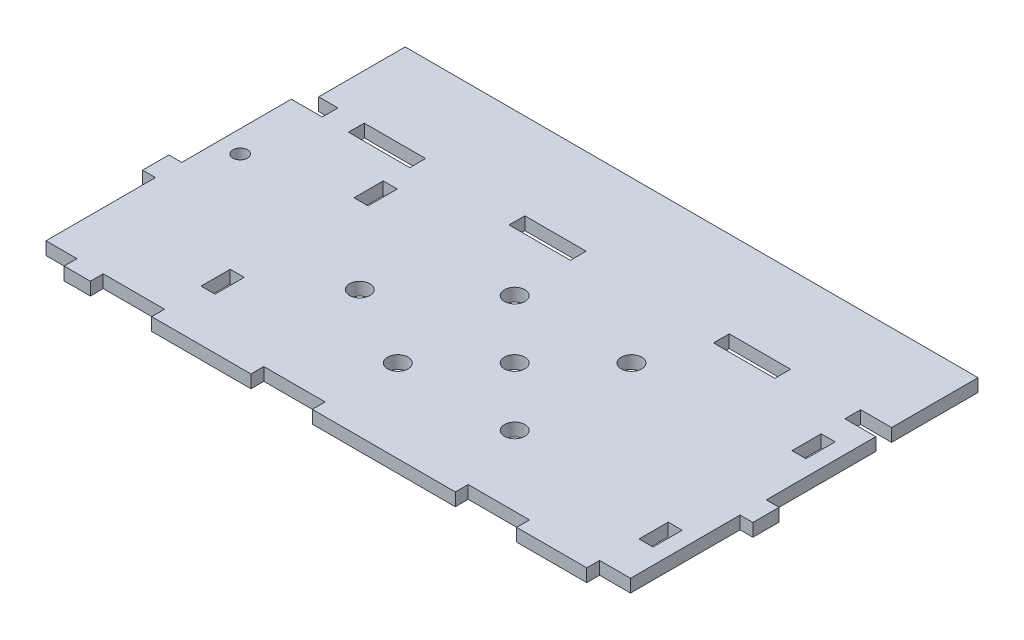
SolidWorks part; units mm, degrees
ref_plane "Front Plane" through (0, 0, 0) normal (0, 0, 1) x (1, 0, 0)
ref_plane "Top Plane" through (0, 0, 0) normal (0, 1, 0) x (1, 0, 0)
ref_plane "Right Plane" through (0, 0, 0) normal (1, 0, 0) x (0, 0, -1)
sketch "Sketch1" plane through (0, 0, 0) normal (0, 1, 0) x (1, 0, 0)
  line L0 (-110.6901, 12.3801) -> (-116.2781, 12.3801)
  line L2 (-110.6901, -46.6749) -> (-110.6901, 0.9501)
  line L4 (143.5639, -46.6749) -> (143.5639, 0.9501)
  line L5 (-110.6901, -46.6749) -> (143.5639, 60.0051) construction
  line L6 (-110.6901, 60.0051) -> (143.5639, -46.6749) construction
  line L7 (-116.2781, 12.3801) -> (-116.2781, 0.9501)
  line L8 (-116.2781, 0.9501) -> (-110.6901, 0.9501)
  line L9 (-110.6901, 12.3801) -> (-110.6901, 60.0051)
  line L10 (10.7219, 63.4341) -> (72.9519, 63.4341) construction
  line L11 (149.1519, 0.9501) -> (143.5639, 0.9501)
  line L12 (149.1519, 12.3801) -> (149.1519, 0.9501)
  line L13 (143.5639, 12.3801) -> (149.1519, 12.3801)
  line L14 (143.5639, 12.3801) -> (143.5639, 60.0051)
  line L23 (-108.712, 0) -> (106.818, 0) construction
  line L32 (-110.6901, 60.0051) -> (-97.2281, 60.0051)
  line L33 (-110.6901, -46.6749) -> (-97.2281, -46.6749)
  line L34 (-85.7981, 60.0051) -> (-59.1281, 60.0051)
  line L36 (-97.2281, 60.0051) -> (-97.2281, 66.8631)
  line L38 (-85.7981, 60.0051) -> (-85.7981, 66.8631)
  line L40 (-59.1281, 60.0051) -> (-59.1281, 66.8631)
  line L42 (-15.9481, 60.0051) -> (-15.9481, 66.8631)
  line L44 (10.7219, 60.0051) -> (10.7219, 66.8631)
  line L46 (72.9519, 60.0051) -> (72.9519, 66.8631)
  line L48 (99.6219, 60.0051) -> (99.6219, 66.8631)
  line L50 (130.1019, 60.0051) -> (130.1019, 66.8631)
  line L51 (-15.9481, 60.0051) -> (10.7219, 60.0051)
  line L52 (72.9519, 60.0051) -> (99.6219, 60.0051)
  line L53 (130.1019, 60.0051) -> (143.5639, 60.0051)
  line L54 (130.1019, -46.6749) -> (130.1019, -52.2629)
  line L55 (99.6219, -52.2629) -> (130.1019, -52.2629)
  line L56 (99.6219, -46.6749) -> (99.6219, -52.2629)
  line L57 (72.9519, -46.6749) -> (72.9519, -52.2629)
  line L58 (10.7219, -52.2629) -> (72.9519, -52.2629)
  line L59 (10.7219, -46.6749) -> (10.7219, -52.2629)
  line L60 (-15.9481, -46.6749) -> (-15.9481, -52.2629)
  line L61 (-59.1281, -52.2629) -> (-15.9481, -52.2629)
  line L62 (-59.1281, -46.6749) -> (-59.1281, -52.2629)
  line L63 (-85.7981, -46.6749) -> (-85.7981, -52.2629)
  line L64 (-97.2281, -52.2629) -> (-85.7981, -52.2629)
  line L65 (-97.2281, -46.6749) -> (-97.2281, -52.2629)
  line L66 (-85.7981, -46.6749) -> (-59.1281, -46.6749)
  line L67 (-15.9481, -46.6749) -> (10.7219, -46.6749)
  line L68 (72.9519, -46.6749) -> (99.6219, -46.6749)
  line L69 (130.1019, -46.6749) -> (143.5639, -46.6749)
  line L70 (130.1019, 66.8631) -> (143.5639, 66.8631)
  line L71 (143.5639, 66.8631) -> (143.5639, 104.4551)
  line L72 (-97.2281, 66.8631) -> (-105.6101, 66.8631)
  line L73 (-105.6101, 66.8631) -> (-105.6101, 104.4551)
  line L74 (-105.6101, 104.4551) -> (143.5639, 104.4551)
  line L75 (99.6219, 66.8631) -> (72.9519, 66.8631)
  line L76 (10.7219, 66.8631) -> (-15.9481, 66.8631)
  line L77 (-59.1281, 66.8631) -> (-85.7981, 66.8631)
  line L78 (-97.2281, 63.4341) -> (-85.7981, 63.4341) construction
  line L79 (-91.5131, 63.4341) -> (-91.5131, -53.3153) construction
  line L80 (-59.1281, 63.4341) -> (-15.9481, 63.4341) construction
  line L81 (-37.5381, 63.4341) -> (-37.5381, -52.2629) construction
  line L82 (41.8369, 63.4341) -> (41.8369, -52.2629) construction
  line L83 (99.6219, 63.4341) -> (130.1019, 63.4341) construction
  line L84 (114.8619, 63.4341) -> (114.8619, -52.2629) construction
  point P0 (0, 0)
  point P57 (-91.5131, -52.2629)
  point P63 (-37.5381, -52.2629)
  point P66 (41.8369, -52.2629)
  dimension "D1" = 106.68
  dimension "D3" = 11.43
  dimension "D4" = 5.588
  dimension "D5" = 6.858
  dimension "D6" = 11.43
  dimension "D7" = 26.67
  dimension "D8" = 13.462
  dimension "D10" = 106.68
  dimension "D11" = 11.43
  dimension "D12" = 6.858
  dimension "D13" = 37.592
  dimension "D14" = 5.588
  dimension "D15" = 5.588
  dimension "D16" = 47.625
  dimension "D17" = 47.625
  dimension "D18" = 47.625
  dimension "D19" = 47.625
  dimension "D20" = 62.23
  dimension "D21" = 11.43
  dimension "D23" = 43.18
  dimension "D26" = 26.67
  dimension "D27" = 30.48
  dimension "D28" = 13.462
  dimension "D29" = 110.6901
  dimension "D30" = 26.67
  dimension "D31" = 43.18
  dimension "D32" = 62.23
  dimension "D33" = 26.67
  dimension "D34" = 30.48
  dimension "D35" = 8.382
extrude "Boss-Extrude1" add sketch "Sketch1" along normal blind 5.588
sketch "Sketch9" plane through (0, 5.588, 0) normal (0, 1, 0) x (1, 0, 0)
  line L0 (-110.6901, 0.9501) -> (-110.6901, -46.6749) construction
  line L1 (-59.8901, -17.3379) -> (-53.7941, -17.3379)
  line L2 (-59.8901, -17.3379) -> (-59.8901, -30.0379)
  line L3 (-59.8901, -30.0379) -> (-53.7941, -30.0379)
  line L4 (-53.7941, -17.3379) -> (-53.7941, -30.0379)
  line L5 (-85.7981, -46.6749) -> (-59.1281, -46.6749) construction
  line L6 (-59.8901, 36.5101) -> (-53.7941, 36.5101)
  line L7 (-59.8901, 36.5101) -> (-59.8901, 49.2101)
  line L8 (-59.8901, 49.2101) -> (-53.7941, 49.2101)
  line L9 (-53.7941, 36.5101) -> (-53.7941, 49.2101)
  line L10 (130.6099, -17.3379) -> (136.7059, -17.3379)
  line L11 (130.6099, -17.3379) -> (130.6099, -30.0379)
  line L12 (130.6099, -30.0379) -> (136.7059, -30.0379)
  line L13 (136.7059, -17.3379) -> (136.7059, -30.0379)
  line L14 (130.6099, 49.2101) -> (136.7059, 49.2101)
  line L15 (130.6099, 49.2101) -> (130.6099, 36.5101)
  line L16 (130.6099, 36.5101) -> (136.7059, 36.5101)
  line L17 (136.7059, 49.2101) -> (136.7059, 36.5101)
  line L18 (143.5639, -46.6749) -> (143.5639, 0.9501) construction
  line L19 (143.5639, 12.3801) -> (143.5639, 60.0051) construction
  dimension "D1" = 12.7
  dimension "D2" = 6.096
  dimension "D3" = 50.8
  dimension "D4" = 16.637
  dimension "D5" = 50.8
  dimension "D6" = 83.185
  dimension "D7" = 12.7
  dimension "D8" = 6.096
  dimension "D9" = 12.7
  dimension "D10" = 6.096
  dimension "D11" = 6.096
  dimension "D12" = 12.7
  dimension "D13" = 6.858
  dimension "D14" = 6.858
extrude "Cut-Extrude1" cut sketch "Sketch9" against normal up to next
sketch "Sketch12" plane through (0, 5.588, 0) normal (0, 1, 0) x (1, 0, 0)
  line L0 (-97.2281, 60.0051) -> (-110.6901, 60.0051) construction
  line L1 (-110.6901, 60.0051) -> (-110.6901, 12.3801) construction
  circle A0 centre (-101.1651, 28.2551) radius 3.175
  point P4 (-103.9591, 60.0051)
  dimension "D1" = 6.35
  dimension "D2" = 31.75
  dimension "D3" = 9.525
extrude "Cut-Extrude2" cut sketch "Sketch12" against normal up to next
sketch "Sketch13" plane through (0, 0, 0) normal (0, -1, 0) x (1, 0, 0)
  line L0 (72.9519, -60.0051) -> (99.6219, -60.0051) construction
  circle A0 centre (62.6731, 16.1949) radius 4.445
  circle A1 centre (11.8731, 16.1949) radius 4.445
  circle A2 centre (11.8731, -34.6051) radius 4.445
  circle A3 centre (62.6731, -34.6051) radius 4.445
  circle A4 centre (37.2731, -9.2051) radius 4.445
  circle A5 centre (-24.0609, -3.175) radius 4.445
  dimension "D1" = 8.89
  dimension "D2" = 50.8
  dimension "D3" = 8.89
  dimension "D4" = 50.8
  dimension "D5" = 50.8
  dimension "D6" = 25.4
  dimension "D7" = 25.4
  dimension "D8" = 25.4
extrude "Cut-Extrude3" cut sketch "Sketch13" against normal up to next
sketch "Sketch14" plane through (0, 5.588, 0) normal (0, 1, 0) x (1, 0, 0)
  line L0 (143.5639, -46.6749) -> (143.5639, 0.9501) construction
  line L1 (137.2139, 0.9501) -> (140.3889, 0.9501)
  line L2 (137.2139, 0.9501) -> (137.2139, 13.6501)
  line L3 (137.2139, 13.6501) -> (140.3889, 13.6501)
  line L4 (140.3889, 0.9501) -> (140.3889, 13.6501)
  line L5 (143.5639, 0.9501) -> (149.1519, 0.9501) construction
  dimension "D1" = 3.175
  dimension "D2" = 12.7
  dimension "D3" = 3.175
